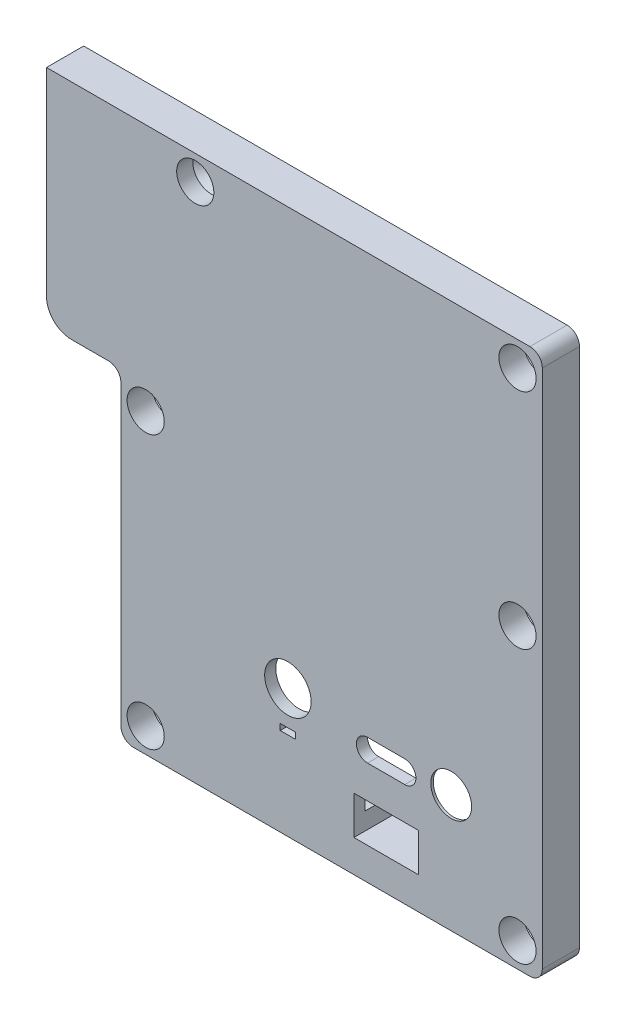
SolidWorks part; units mm, degrees
ref_plane "前视基准面" through (0, 0, 0) normal (0, 0, 1) x (1, 0, 0)
ref_plane "上视基准面" through (0, 0, 0) normal (0, 1, 0) x (1, 0, 0)
ref_plane "右视基准面" through (0, 0, 0) normal (1, 0, 0) x (0, 0, -1)
sketch "草图1" plane through (0, 0, 0) normal (0, 0, 1) x (1, 0, 0)
  line L0 (0, 0) -> (68, 0)
  line L1 (68, 0) -> (68, 88)
  line L2 (68, 88) -> (8, 88)
  line L3 (8, 88) -> (8, 52)
  line L4 (8, 52) -> (0, 52)
  line L5 (0, 52) -> (0, 0)
  line L6 (2.2, 49.8) -> (2.2, 2.2)
  line L7 (2.2, 2.2) -> (65.8, 2.2)
  line L8 (65.8, 2.2) -> (65.8, 85.8)
  line L9 (65.8, 85.8) -> (10.2, 85.8)
  line L10 (10.2, 85.8) -> (10.2, 49.8)
  line L11 (10.2, 49.8) -> (2.2, 49.8)
  line L12 (8, 44) -> (8, 8)
  line L13 (8, 8) -> (60, 8)
  line L14 (60, 8) -> (60, 80)
  line L15 (60, 80) -> (16, 80)
  line L16 (16, 80) -> (16, 44)
  line L17 (16, 44) -> (8, 44)
  dimension "D1" = 8
  dimension "D2" = 68
  dimension "D3" = 36
  dimension "D4" = 88
  dimension "D5" = 2.2
  dimension "D6" = 8
extrude "凸台-拉伸1" add sketch "草图1" against normal blind 6 contours L5 L0 L1 L2 L3 L4
extrude "凸台-拉伸4" add sketch "草图1<2>" against normal blind 6.8 contours L10 L11 L6 L7 L8 L9 region at (6.2, 48.7496, 0)
sketch "草图1<2>" plane through (0, 0, 0) normal (0, 0, 1) x (1, 0, 0) same geometry as "草图1"
extrude "切除-拉伸6" cut sketch "草图1<5>" against normal through all from offset 1.8 contours L16 L17 L12 L13 L14 L15 region at (35.8333, 42.5, 0) offset against normal yes
sketch "草图1<5>" plane through (0, 0, 0) normal (0, 0, 1) x (1, 0, 0) same geometry as "草图1"
fillet "圆角1" radius 2 8 edges at (68, 0, -3) (0, 0, -3) (68, 88, -3) (2.2, 2.2, -6.4) (65.8, 2.2, -6.4) (65.8, 85.8, -6.4) (10.2, 85.8, -6.4) (2.2, 49.8, -6.4)
sketch "草图4" plane through (0, 0, 0) normal (0, 0, 1) x (1, 0, 0)
  line L0 (61, 81) -> (67, 81)
  line L1 (9, 87) -> (15, 87)
  line L2 (9, 87) -> (9, 81)
  line L3 (9, 81) -> (15, 81)
  line L4 (15, 87) -> (15, 81)
  line L5 (9, 87) -> (15, 81) construction
  line L6 (9, 81) -> (15, 87) construction
  line L7 (67, 87) -> (67, 81)
  line L8 (61, 87) -> (61, 81)
  line L9 (61, 87) -> (67, 81) construction
  line L10 (61, 81) -> (67, 87) construction
  line L11 (61, 87) -> (67, 87)
  line L12 (61, 1) -> (67, 1)
  line L13 (67, 7) -> (67, 1)
  line L14 (61, 7) -> (61, 1)
  line L15 (61, 7) -> (67, 1) construction
  line L16 (61, 1) -> (67, 7) construction
  line L17 (61, 7) -> (67, 7)
  line L18 (1, 45) -> (7, 45)
  line L19 (7, 51) -> (7, 45)
  line L20 (1, 51) -> (1, 45)
  line L21 (1, 51) -> (7, 45) construction
  line L22 (1, 45) -> (7, 51) construction
  line L23 (1, 51) -> (7, 51)
  line L24 (1, 1) -> (7, 1)
  line L25 (7, 7) -> (7, 1)
  line L26 (1, 7) -> (1, 1)
  line L27 (1, 7) -> (7, 1) construction
  line L28 (1, 1) -> (7, 7) construction
  line L29 (1, 7) -> (7, 7)
  line L30 (61, 51) -> (67, 51)
  line L31 (61, 51) -> (67, 45) construction
  line L32 (67, 51) -> (67, 45)
  line L33 (61, 45) -> (67, 45)
  line L34 (61, 45) -> (67, 51) construction
  line L35 (61, 51) -> (61, 45)
  line L36 (2, 0) -> (66, 0) construction
  line L37 (0, 52) -> (0, 2) construction
  line L38 (66, 88) -> (8, 88) construction
  line L39 (8, 88) -> (8, 52) construction
  circle A0 centre (12, 84) radius 1.6
  circle A1 centre (64, 84) radius 1.6
  circle A2 centre (64, 4) radius 1.6
  circle A3 centre (4, 48) radius 1.6
  circle A4 centre (4, 4) radius 1.6
  circle A5 centre (64, 48) radius 1.6
  circle A6 centre (12, 84) radius 3
  circle A7 centre (64, 84) radius 3
  circle A8 centre (4, 48) radius 3
  circle A9 centre (64, 48) radius 3
  circle A10 centre (4, 4) radius 3
  circle A11 centre (64, 4) radius 3
  dimension "D1" = 3.2
  dimension "D8" = 44
  dimension "D9" = 36
  dimension "D10" = 52
  dimension "D11" = 60
  dimension "D12" = 60
  dimension "D13" = 4
  dimension "D14" = 4
  dimension "D15" = 4
  dimension "D16" = 4
  dimension "D2" = 6
  dimension "D3" = 6
  dimension "D4" = 6
  dimension "D5" = 6
  dimension "D6" = 6
  dimension "D7" = 6
extrude "切除-拉伸4" cut sketch "草图4" against normal through all and the other way through all contours A0 | A1 | A5 | A3 | A4 | A2
sketch "草图5" plane through (0, 0, 0) normal (0, 0, 1) x (1, 0, 0)
  line L0 (39.8, -18.5) -> (45.8, -18.5) construction
  line L1 (25.7, -15.2) -> (28.2, -15.2)
  line L2 (25.7, -15.2) -> (25.7, -14.2)
  line L3 (25.7, -14.2) -> (28.2, -14.2)
  line L4 (28.2, -15.2) -> (28.2, -14.2)
  line L5 (25.7, -15.2) -> (28.2, -14.2) construction
  line L6 (25.7, -14.2) -> (28.2, -15.2) construction
  line L7 (37.6, -11.4) -> (48, -11.4)
  line L8 (37.6, -11.4) -> (37.6, -5.2)
  line L9 (37.6, -5.2) -> (48, -5.2)
  line L10 (48, -11.4) -> (48, -5.2)
  line L11 (37.6, -11.4) -> (48, -5.2) construction
  line L12 (37.6, -5.2) -> (48, -11.4) construction
  line L13 (39.8, -16.7) -> (45.8, -16.7)
  line L14 (39.8, -20.3) -> (45.8, -20.3)
  line L15 (48.6, -23.8) -> (58, -23.8)
  line L16 (48.6, -23.8) -> (48.6, -12.4)
  line L17 (48.6, -12.4) -> (58, -12.4)
  line L18 (58, -23.8) -> (58, -12.4)
  line L19 (8, -27.8) -> (60, -27.8)
  line L20 (8, -27.8) -> (8, -4)
  line L21 (8, -4) -> (60, -4)
  line L22 (60, -27.8) -> (60, -4)
  line L23 (2, 0) -> (66, 0) construction
  line L24 (0, 52) -> (0, 2) construction
  line L25 (2, 0) -> (66, 0) construction
  line L26 (37.6, 5.2) -> (48, 11.4) construction
  line L27 (37.6, 11.4) -> (48, 5.2) construction
  line L28 (25.7, 14.2) -> (28.2, 15.2) construction
  line L29 (25.7, 15.2) -> (28.2, 14.2) construction
  line L34 (58, 23.8) -> (58, 12.4)
  line L35 (48.6, 12.4) -> (58, 12.4)
  line L36 (48.6, 23.8) -> (48.6, 12.4)
  line L37 (48.6, 23.8) -> (58, 23.8)
  line L38 (48, 11.4) -> (48, 5.2)
  line L39 (37.6, 5.2) -> (48, 5.2)
  line L40 (37.6, 11.4) -> (37.6, 5.2)
  line L41 (37.6, 11.4) -> (48, 11.4)
  line L42 (28.2, 15.2) -> (28.2, 14.2)
  line L43 (25.7, 14.2) -> (28.2, 14.2)
  line L44 (25.7, 15.2) -> (25.7, 14.2)
  line L45 (25.7, 15.2) -> (28.2, 15.2)
  line L46 (39.8, 18.5) -> (45.8, 18.5) construction
  line L47 (39.8, 16.7) -> (45.8, 16.7)
  line L48 (39.8, 20.3) -> (45.8, 20.3)
  circle A0 centre (26.95, -20.7) radius 3.75
  arc A1 (39.8, -16.7) -> (39.8, -20.3) centre (39.8, -18.5) ccw
  arc A2 (45.8, -20.3) -> (45.8, -16.7) centre (45.8, -18.5) ccw
  circle A3 centre (53.3, -19) radius 3.3
  circle A4 centre (53.3, 19) radius 3.3
  circle A5 centre (26.95, 20.7) radius 3.75
  arc A6 (39.8, 16.7) -> (39.8, 20.3) centre (39.8, 18.5) cw
  arc A7 (45.8, 20.3) -> (45.8, 16.7) centre (45.8, 18.5) cw
  point P2 (26.95, -14.7)
  point P8 (42.8, -8.3)
  point P14 (42.8, -18.5)
  point P25 (53.3, -23.8)
  point P30 (0, 0)
  point P52 (42.8, 18.5)
  point P58 (42.8, 8.3)
  point P59 (26.95, 14.7)
  dimension "D1" = 7.5
  dimension "D9" = 1.8
  dimension "D12" = 6.6
  dimension "D2" = 1
  dimension "D3" = 2.5
  dimension "D4" = 5.5
  dimension "D5" = 10.4
  dimension "D6" = 6.2
  dimension "D7" = 5.3
  dimension "D8" = 6
  dimension "D10" = 9.4
  dimension "D11" = 11.4
  dimension "D13" = 4.8
  dimension "D14" = 0.6
  dimension "D15" = 1
  dimension "D16" = 9.4
  dimension "D17" = 2.8
  dimension "D18" = 52
  dimension "D19" = 2
  dimension "D20" = 1.2
  dimension "D21" = 4
  dimension "D22" = 23.8
  dimension "D23" = 23.8
  dimension "D24" = 4
  dimension "D25" = 8
extrude "切除-拉伸5" cut sketch "草图5" against normal through all contours A5 | L41 L40 L39 L38 | L45 L44 L43 L42 | L35 L34 L37 L36 | L47 A7 L48 A6 region at (42.8, 8.3, 0) region at (26.95, 14.7, 0) region at (26.95, 20.7, 0)
extrude "凸台-拉伸5" add sketch "草图5<3>" against normal blind 0.4 contours L37 L36 L35 L34 A4 region at (57.8522, 18.1, 0)
sketch "草图5<3>" plane through (0, 0, 0) normal (0, 0, 1) x (1, 0, 0) same geometry as "草图5"
sketch "草图6" plane through (0, 0, 0) normal (0, 0, 1) x (1, 0, 0)
  line L1 (8, 52) -> (-12, 52)
  line L2 (8, 52) -> (8, 88)
  line L3 (8, 88) -> (-12, 88)
  line L4 (-12, 52) -> (-12, 88)
  dimension "D1" = 20
extrude "凸台-拉伸7" add sketch "草图6" against normal blind 6
fillet "圆角2" radius 2 1 edges at (0, 52, -3)
fillet "圆角3" radius 4 1 edges at (-12, 52, -3)
sketch "草图7" plane through (-12, 0, 0) normal (-1, 0, 0) x (0, 0, 1)
  line L0 (-6, 88) -> (0, 88) construction
  circle A0 centre (-3, 82) radius 1.4
  circle A1 centre (-3, 62) radius 1.4
  dimension "D1" = 2.8
  dimension "D3" = 20
  dimension "D2" = 6
extrude "切除-拉伸7" cut sketch "草图7" against normal blind 20
extrude "切除-拉伸8" cut sketch "草图4<3>" against normal blind 4 contours A6 A0 | A7 A1 | A8 A3 | A9 A5 | A10 A4 | A11 A2 region at (61.9387, 81.9387, 0) region at (14.0613, 86.0613, 0) region at (61.9387, 1.9387, 0) region at (1.9387, 45.9387, 0) region at (1.9387, 1.9387, 0) region at (66.0613, 50.0613, 0)
sketch "草图4<3>" plane through (0, 0, 0) normal (0, 0, 1) x (1, 0, 0) same geometry as "草图4"
sketch "草图8" plane through (0, 0, 0) normal (0, -1, 0) x (1, 0, 0)
  line L0 (68, 0) -> (68, -6) construction
  line L1 (0, -6) -> (0, 0) construction
  circle A0 centre (58, -3) radius 1.4
  circle A1 centre (10, -3) radius 1.4
  circle A2 centre (34, -3) radius 1.4
  dimension "D1" = 2.8
  dimension "D2" = 10
  dimension "D3" = 10
  dimension "D4" = 48
  dimension "D5" = 24
extrude "切除-拉伸9" cut sketch "草图8" against normal blind 7
chamfer "倒角1" distance 1.4 angle 45 6 edges at (65.6, 4, -4) (5.6, 4, -4) (5.6, 48, -4) (65.6, 48, -4) (65.6, 84, -4) (15, 84, -4)
